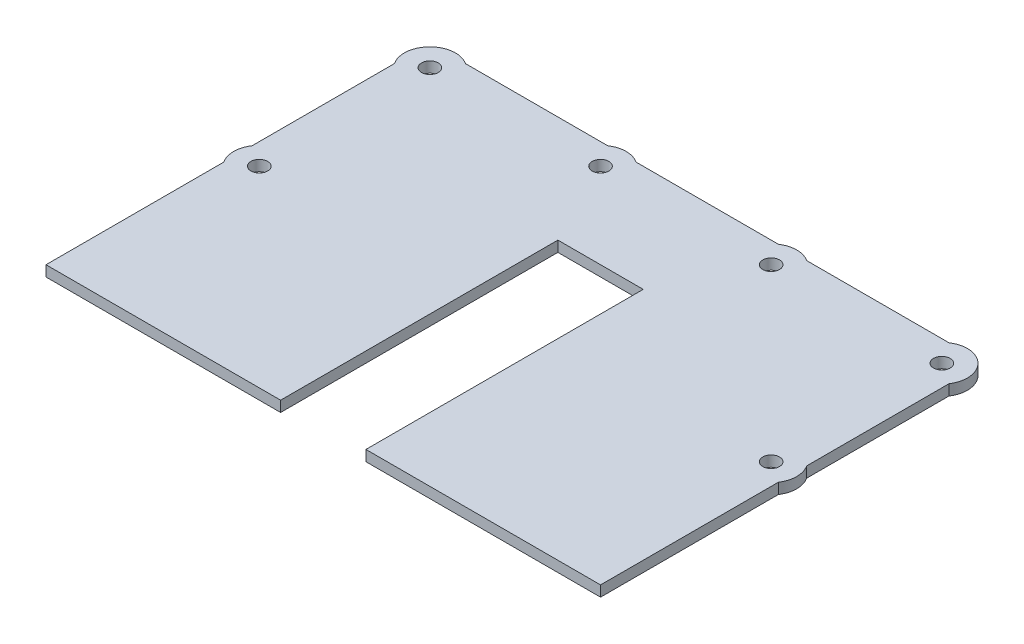
SolidWorks part; units mm, degrees
material "Alum Plate"
ref_plane "Front Plane" through (0, 0, 0) normal (0, 0, 1) x (1, 0, 0)
ref_plane "Top Plane" through (0, 0, 0) normal (0, 1, 0) x (1, 0, 0)
ref_plane "Right Plane" through (0, 0, 0) normal (1, 0, 0) x (0, 0, -1)
other "Bounding Box"
ref_plane "Default Plane" through (0, 2.286, 19.05) normal (0, -1, 0) x (-1, 0, 0)
sketch "Sketch1" plane through (0, 0, 0) normal (0, 1, 0) x (1, 0, 0)
  line L0 (-103.7379, 114.3) -> (-61.3621, 114.3)
  line L1 (-165.1, 0) -> (-95.25, 0)
  line L2 (0, 0) -> (-69.85, 0)
  line L3 (-95.25, 0) -> (-95.25, 82.55)
  line L4 (-95.25, 82.55) -> (-69.85, 82.55)
  line L5 (-69.85, 82.55) -> (-69.85, 0)
  circle A0 centre (-6.35, 57.15) radius 2.4892
  circle A1 centre (-6.35, 107.95) radius 2.4892
  circle A2 centre (-57.15, 107.95) radius 2.4892
  circle A3 centre (-107.95, 107.95) radius 2.4892
  circle A4 centre (-158.75, 107.95) radius 2.4892
  circle A5 centre (-158.75, 57.15) radius 2.4892
  line B0 (0, 52.9379) -> (0, 0)
  line B1 (0, 103.7379) -> (0, 61.3621)
  line B2 (-52.9379, 114.3) -> (-10.5621, 114.3)
  line B3 (-154.5379, 114.3) -> (-112.1621, 114.3)
  line B4 (-165.1, 61.3621) -> (-165.1, 103.7379)
  line B5 (-165.1, 0) -> (-165.1, 52.9379)
  circle B6 centre (-158.75, 57.15) radius 2.0193
  circle B7 centre (-158.75, 107.95) radius 2.0193
  circle B8 centre (-107.95, 107.95) radius 2.0193
  circle B9 centre (-57.15, 107.95) radius 2.0193
  circle B10 centre (-6.35, 107.95) radius 2.0193
  circle B11 centre (-6.35, 57.15) radius 2.0193
  arc B12 (0, 52.9379) -> (0, 61.3621) centre (-6.35, 57.15) ccw
  arc B13 (0, 103.7379) -> (-10.5621, 114.3) centre (-6.35, 107.95) ccw
  arc B14 (-52.9379, 114.3) -> (-61.3621, 114.3) centre (-57.15, 107.95) ccw
  arc B15 (-103.7379, 114.3) -> (-112.1621, 114.3) centre (-107.95, 107.95) ccw
  arc B16 (-154.5379, 114.3) -> (-165.1, 103.7379) centre (-158.75, 107.95) ccw
  arc B17 (-165.1, 61.3621) -> (-165.1, 52.9379) centre (-158.75, 57.15) ccw
  dimension "D1" = 4.9784
  dimension "D2" = 4.9784
  dimension "D3" = 4.9784
  dimension "D4" = 4.9784
  dimension "D5" = 4.9784
  dimension "D6" = 4.9784
  dimension "D7" = 69.85
  dimension "D8" = 82.55
sketch_block_instance "Block-bottomplateblock-1"
sketch_block "Block-bottomplateblock"
extrude "Boss-Extrude1" add sketch "Sketch1" along normal blind 3.175 contours B4 B17 B5 L1 L3 L4 L5 L2 B0 B12 B1 B13 B2 B14 L0 B15 B3 B16 A0 A1 A2 A3 A4 A5 region at (-82.55, 0, -112.2638)
sketch "Sketch2" plane through (-165.1, 0, 0) normal (-1, 0, 0) x (0, 0, 1)
  line L2 (3.8023, 0) -> (0, 3.175)
  line L3 (0, 0) -> (3.8023, 0)
  dimension "D1" = 4.9536
sketch "Sketch3" plane through (-165.1, 0, 0) normal (-1, 0, 0) x (0, 0, 1)
  line L0 (0, 0) -> (0, 3.175)
sketch "Sketch7" plane through (0, 3.175, 0) normal (0, 1, 0) x (1, 0, 0)
  line L0 (-165.1, 0) -> (-165.1, -3.8023) construction
  line L2 (-95.25, 0) -> (-165.1, 0)
  line L3 (-95.25, 0) -> (-95.25, -3.8023)
  line L4 (-95.25, -3.8023) -> (-165.1, -3.8023)
  line L5 (-165.1, 0) -> (-165.1, -3.8023)
  line L6 (-69.85, 0) -> (0, 0)
  line L7 (-69.85, 0) -> (-69.85, -3.8023)
  line L8 (-69.85, -3.8023) -> (0, -3.8023)
  line L9 (0, 0) -> (0, -3.8023)
extrude "Boss-Extrude2" add sketch "Sketch7" against normal blind 3.175 contours L7 L6 L9 L8
sketch "Sketch8" plane through (0, 0, 0) normal (0, -1, 0) x (1, 0, 0)
  line L0 (-165.1, 0) -> (-165.1, 3.8023) construction
  line L1 (-165.1, 3.8023) -> (-95.25, 3.8023)
  line L2 (-165.1, 3.8023) -> (-165.1, 0)
  line L3 (-165.1, 0) -> (-95.25, 0)
  line L4 (-95.25, 3.8023) -> (-95.25, 0)
  line L5 (-165.1, 3.8023) -> (-165.1, 0) construction
extrude "Boss-Extrude4" add sketch "Sketch8" against normal blind 3.175
sketch "Sketch9" plane through (-165.1, 0, 0) normal (-1, 0, 0) x (0, 0, 1)
  line L0 (0, 3.175) -> (3.8023, 0)
  line L1 (3.8023, 0) -> (3.8023, 3.175)
  line L2 (3.8023, 3.175) -> (0, 3.175)
extrude "Cut-Extrude1" cut sketch "Sketch9" against normal through all
sketch "Sketch10" plane through (-165.1, 0, 0) normal (-1, 0, 0) x (0, 0, 1)
  line L1 (0, 0) -> (3.825, 0)
  line L2 (0, 0) -> (0, 3.2279)
  line L3 (0, 3.2279) -> (3.825, 3.2279)
  line L4 (3.825, 0) -> (3.825, 3.2279)
extrude "Cut-Extrude2" cut sketch "Sketch10" against normal through all
equation "\"Unit Measure\"= \"BoundingVolume\" / \"Thickness\"'in^2"
